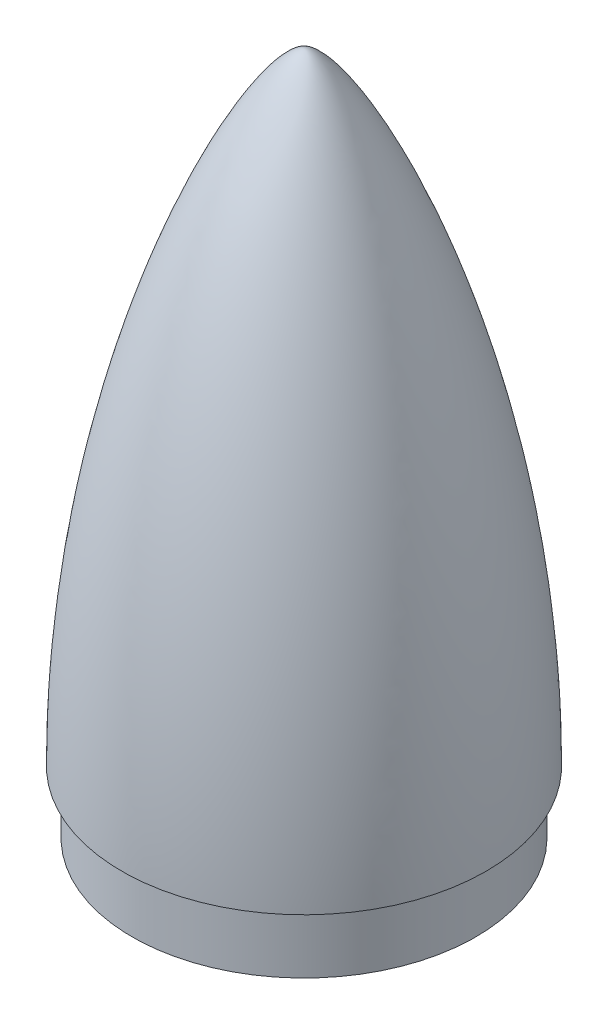
SolidWorks part; units mm, degrees
ref_plane "Front Plane" through (0, 0, 0) normal (0, 0, 1) x (1, 0, 0)
ref_plane "Top Plane" through (0, 0, 0) normal (0, 1, 0) x (1, 0, 0)
ref_plane "Right Plane" through (0, 0, 0) normal (1, 0, 0) x (0, 0, -1)
sketch "Sketch1" plane through (0, 0, 0) normal (0, 0, 1) x (1, 0, 0)
  line L0 (0, 0) -> (0, 150) construction
  line L1 (0, 0) -> (41.5, 0) construction
  line L2 (41.5, 0) -> (44, 0)
  line L3 (44, -30.0639) -> (44, 30.0639) construction
  line L4 (15.6538, 150) -> (-15.6538, 150) construction
  line L5 (41.5, 0) -> (41.5, -15)
  line L6 (41.5, -15) -> (38, -15)
  line L7 (38, -15) -> (38, 2)
  line L8 (38, -15) -> (38, 4.4079) construction
  line L9 (38, 2) -> (42.7434, 2)
  line L10 (0, 150) -> (0, 148.75)
  line L12 (40.25, 1.25) -> (40.25, -13.75) construction
  line L13 (39.25, -13.75) -> (39.25, 4.4079) construction
  line L14 (40.25, -13.75) -> (39.25, -13.75) construction
  line L15 (40.25, 1.25) -> (42.7474, 1.25) construction
  spline S0 degree 3 poles (0, 150) (9.015, 150) (44, 84.4071) (44, 0) knots 0 0 0 0 1 1 1 1
  spline S1 degree 1 poles (0, 148.75) (42.7474, 1.25) knots 0 0 1 1 construction
  spline S2 degree 3 poles (0, 148.75) (0.0624, 148.75) (0.1617, 148.7395) (0.554, 148.6308) (1.2375, 148.2745) (2.2943, 147.4539) (3.5152, 146.2543) (4.8695, 144.6904) (6.8229, 142.1383) (9.4994, 138.103) (12.9776, 131.9924) (17.844, 122.2536) (24.1264, 107.2762) (30.0794, 89.0236) (34.2913, 72.73) (37.0869, 59.7323) (39.4313, 46.0243) (41.2369, 31.6771) (42.2195, 19.2348) (42.6356, 9.3515) (42.728, 4.3535) (42.7451, 1.7504) (42.7467, 1.4363) (42.7474, 1.25) knots 0 0 0 0 0.015547 0.031095 0.06219 0.093285 0.12438 0.155475 0.18657 0.248759 0.310949 0.373139 0.497519 0.621899 0.684089 0.746278 0.808468 0.870658 0.932848 0.963943 0.99131 0.992801 0.995038 0.995038 0.995038 0.995038 only from (0, 148.75) to (42.7434, 2)
  point P18 (0, 0)
  point P19 (0, 148.75)
  dimension "D4" = 1.25
  dimension "D1" = 41.5
  dimension "D2" = 2.5
  dimension "D3" = 150
  dimension "D5" = 3.5
  dimension "D6" = 15
  dimension "D7" = 2
revolve "Revolve1" add sketch "Sketch1" angle 360 about L0
